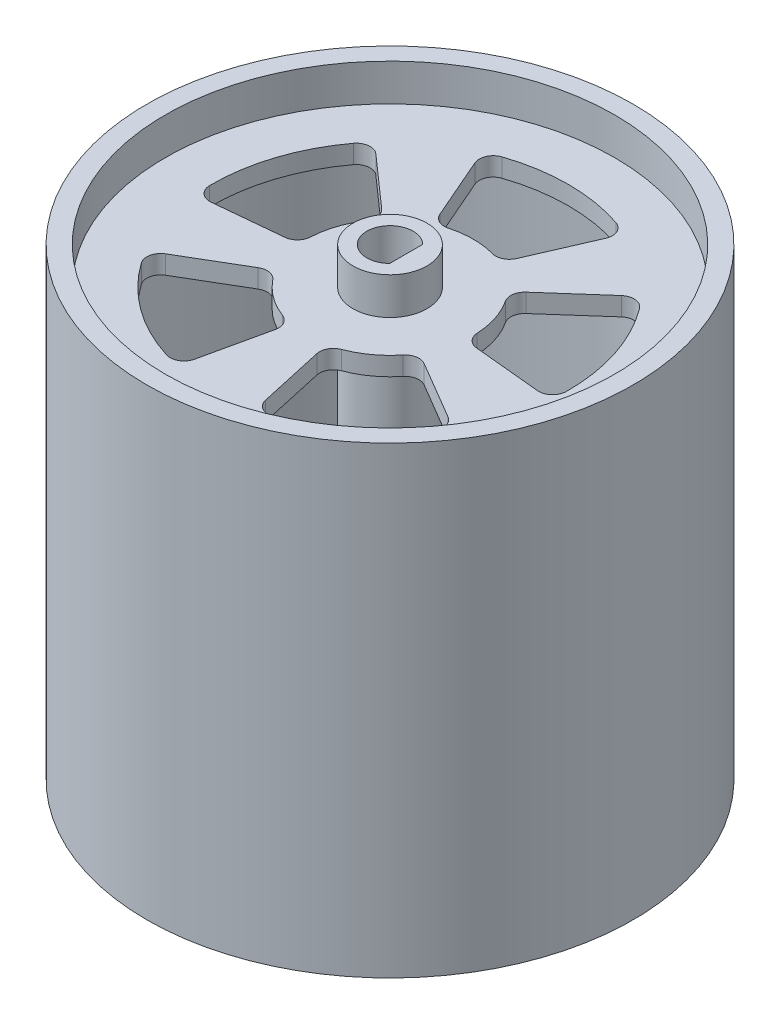
SolidWorks part; units mm, degrees
ref_plane "Front Plane" through (0, 0, 0) normal (0, 0, 1) x (1, 0, 0)
ref_plane "Top Plane" through (0, 0, 0) normal (0, 1, 0) x (1, 0, 0)
ref_plane "Right Plane" through (0, 0, 0) normal (1, 0, 0) x (0, 0, -1)
sketch "Sketch1" plane through (0, 0, 0) normal (0, 1, 0) x (1, 0, 0)
  circle A0 centre (0, 0) radius 52.5
  circle A1 centre (0, 0) radius 48.5
  dimension "D1" = 105
  dimension "D2" = 97
extrude "Boss-Extrude1" add sketch "Sketch1" along normal blind 100
sketch "Sketch2" plane through (0, 0, 0) normal (0, -1, 0) x (1, 0, 0)
  line L0 (7.6561, 34.5345) -> (4.4986, 20.2919)
  line L1 (7.6085, 2.4721) -> (46.1262, 14.9873)
  line L2 (0, 8) -> (0, 48.5)
  line L3 (30.4784, 17.9532) -> (17.9086, 10.549)
  line L4 (35.2102, 3.3904) -> (20.6889, 1.9921)
  line L5 (26.4928, -23.4389) -> (15.5668, -13.7723)
  line L6 (14.105, -32.4392) -> (8.2878, -19.0607)
  line L7 (-14.105, -32.4392) -> (-8.2878, -19.0607)
  line L8 (-26.4928, -23.4389) -> (-15.5668, -13.7723)
  line L9 (-35.2102, 3.3904) -> (-20.6889, 1.9921)
  line L10 (-30.4784, 17.9532) -> (-17.9086, 10.549)
  line L11 (-7.6561, 34.5345) -> (-4.4986, 20.2919)
  line L12 (3.5, 3.5707) -> (3.5, -3.5707)
  arc A0 (46.1262, 14.9873) -> (0, 48.5) centre (0, 0) ccw
  circle A1 centre (0, 0) radius 5
  circle A2 centre (0, 0) radius 8
  arc A3 (14.0452, 11.2576) -> (6.3664, 16.8365) centre (0, 0) ccw
  arc A4 (31.4028, 22.2737) -> (11.4795, 36.7488) centre (0, 0) ccw
  arc A5 (6.3664, 16.8365) -> (4.4986, 20.2919) centre (7.4275, 19.6426) cw
  arc A6 (17.9086, 10.549) -> (14.0452, 11.2576) centre (16.386, 13.1339) cw
  arc A7 (31.4028, 22.2737) -> (30.4784, 17.9532) centre (28.9558, 20.538) cw
  arc A8 (11.4795, 36.7488) -> (7.6561, 34.5345) centre (10.585, 33.8852) ccw
  arc A9 (38.4975, 0.4383) -> (35.2102, 3.3904) centre (35.4977, 0.4042) ccw
  arc A10 (30.8875, -22.9829) -> (38.4975, 0.4383) centre (0, 0) ccw
  arc A11 (30.8875, -22.9829) -> (26.4928, -23.4389) centre (28.4807, -21.192) cw
  arc A12 (15.5668, -13.7723) -> (15.0468, -9.8789) centre (17.5546, -11.5254) cw
  arc A13 (15.0468, -9.8789) -> (17.9798, -0.8521) centre (0, 0) ccw
  arc A14 (17.9798, -0.8521) -> (20.6889, 1.9921) centre (20.9765, -0.9941) cw
  arc A15 (12.3132, -36.4779) -> (14.105, -32.4392) centre (11.3538, -33.6354) ccw
  arc A16 (-12.3132, -36.4779) -> (12.3132, -36.4779) centre (0, 0) ccw
  arc A17 (-12.3132, -36.4779) -> (-14.105, -32.4392) centre (-11.3538, -33.6354) cw
  arc A18 (-8.2878, -19.0607) -> (-4.7457, -17.3631) centre (-5.5367, -20.257) cw
  arc A19 (-4.7457, -17.3631) -> (4.7457, -17.3631) centre (0, 0) ccw
  arc A20 (4.7457, -17.3631) -> (8.2878, -19.0607) centre (5.5367, -20.257) cw
  arc A21 (-30.8875, -22.9829) -> (-26.4928, -23.4389) centre (-28.4807, -21.192) ccw
  arc A22 (-38.4975, 0.4383) -> (-30.8875, -22.9829) centre (0, 0) ccw
  arc A23 (-38.4975, 0.4383) -> (-35.2102, 3.3904) centre (-35.4977, 0.4042) cw
  arc A24 (-20.6889, 1.9921) -> (-17.9798, -0.8521) centre (-20.9765, -0.9941) cw
  arc A25 (-17.9798, -0.8521) -> (-15.0468, -9.8789) centre (0, 0) ccw
  arc A26 (-15.0468, -9.8789) -> (-15.5668, -13.7723) centre (-17.5546, -11.5254) cw
  arc A27 (-31.4028, 22.2737) -> (-30.4784, 17.9532) centre (-28.9558, 20.538) ccw
  arc A28 (-11.4795, 36.7488) -> (-31.4028, 22.2737) centre (0, 0) ccw
  arc A29 (-11.4795, 36.7488) -> (-7.6561, 34.5345) centre (-10.585, 33.8852) cw
  arc A30 (-4.4986, 20.2919) -> (-6.3664, 16.8365) centre (-7.4275, 19.6426) cw
  arc A31 (-6.3664, 16.8365) -> (-14.0452, 11.2576) centre (0, 0) ccw
  arc A32 (-14.0452, 11.2576) -> (-17.9086, 10.549) centre (-16.386, 13.1339) cw
  point P71 (0, 0)
  circle M12 centre (0, 0) radius 48.5
  dimension "D1" = 97
  dimension "D2" = 10
  dimension "D3" = 3
  dimension "D6" = 10
  dimension "D7" = 10
  dimension "D10" = 3
  dimension "D4" = 72
  dimension "D5" = 72
  dimension "D8" = 12.5
  dimension "D9" = 12.5
  dimension "D12" = 3.5
  dimension "D11" = 5
extrude "Boss-Extrude2" add sketch "Sketch2" against normal blind 100 separate body contours A2 A1 | L12 A1 region at (7.678, 0, 1.2161) region at (4.1085, 0, 0)
extrude "Boss-Extrude3" add sketch "Sketch2<3>" against normal blind 4 from offset 8 contours A2 L1 L2 A8 A4 A7 L3 A6 A3 A5 L0 M12 | A2 L2 L1 A13 A14 L4 A9 A10 A11 L5 A12 A19 A20 L6 A15 A16 A17 L7 A18 A25 A26 L8 A21 A22 A23 L9 A24 A31 A32 L10 A27 A28 A29 L11 A30 M12 region at (5.0853, 0, 6.9993) region at (-4.7092, 0, -6.4817) offset against normal yes
sketch "Sketch2<3>" plane through (0, 0, 0) normal (0, -1, 0) x (1, 0, 0) same geometry as "Sketch2"
extrude "Boss-Extrude4" add sketch "Sketch2<4>" against normal blind 4 from offset 88 contours A2 L2 L1 A13 A14 L4 A9 A10 A11 L5 A12 A19 A20 L6 A15 A16 A17 L7 A18 A25 A26 L8 A21 A22 A23 L9 A24 A31 A32 L10 A27 A28 A29 L11 A30 M12 | A2 L1 L2 A8 A4 A7 L3 A6 A3 A5 L0 M12 region at (5.0853, 0, 6.9993) region at (-4.7092, 0, -6.4817) offset against normal yes
sketch "Sketch2<4>" plane through (0, 0, 0) normal (0, -1, 0) x (1, 0, 0) same geometry as "Sketch2"
